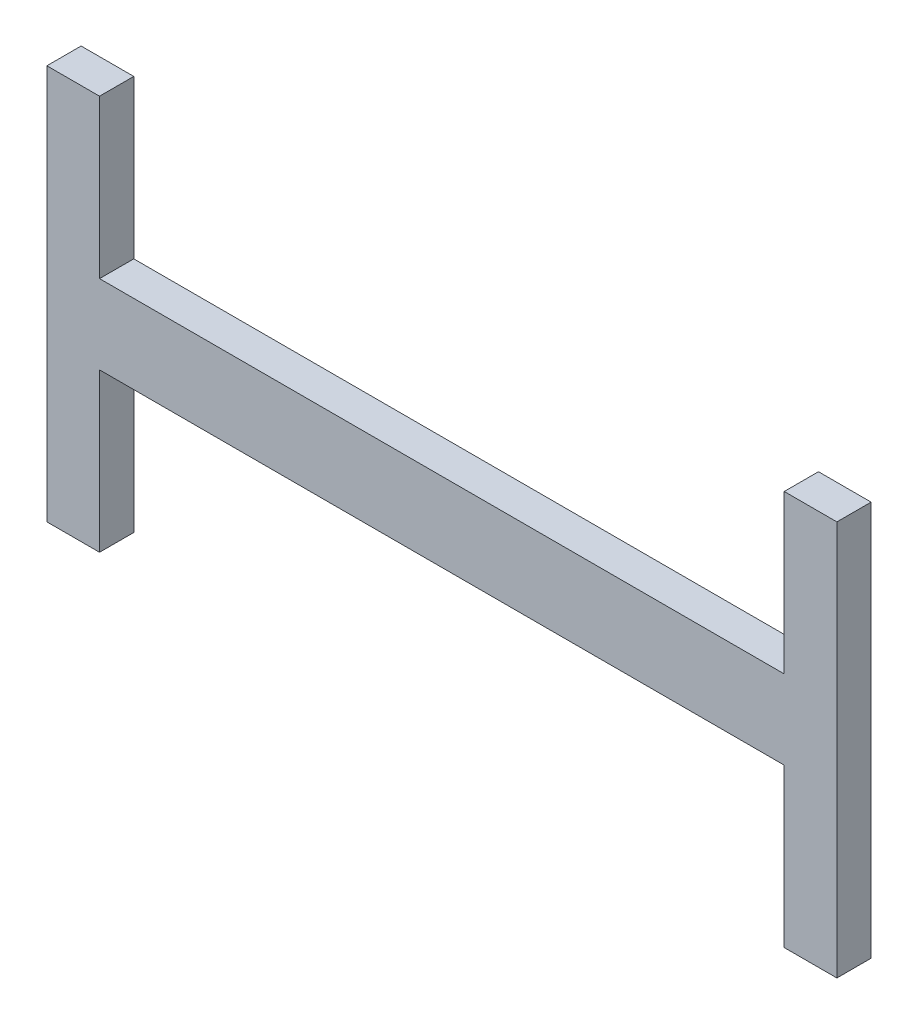
SolidWorks part; units mm, degrees
ref_plane "Plan de face" through (0, 0, 0) normal (0, 0, 1) x (1, 0, 0)
ref_plane "Plan de dessus" through (0, 0, 0) normal (0, 1, 0) x (1, 0, 0)
ref_plane "Plan de droite" through (0, 0, 0) normal (1, 0, 0) x (0, 0, -1)
sketch "Esquisse1" plane through (0, 0, 0) normal (0, 0, 1) x (1, 0, 0)
  line L1 (0, 0) -> (3000, 0)
  line L2 (0, 0) -> (0, 1500)
  line L3 (0, 1500) -> (3000, 1500)
  line L4 (3000, 0) -> (3000, 1500)
  dimension "D1" = 3000
  dimension "D2" = 1500
extrude "Boss.-Extru.1" add sketch "Esquisse1" against normal blind 130 contours L3 L4 L1 L2
sketch "Esquisse3" plane through (0, 0, 0) normal (0, 0, 1) x (1, 0, 0)
  line L0 (200, 1500) -> (200, 900)
  line L1 (0, 1500) -> (3000, 1500) construction
  line L2 (200, 900) -> (2800, 900)
  line L3 (2800, 900) -> (2800, 1500)
  line L4 (200, 1500) -> (2800, 1500)
  line L5 (0, 0) -> (0, 1500) construction
  line L6 (3000, 0) -> (3000, 1500) construction
  line L7 (200, 0) -> (200, 600)
  line L8 (0, 0) -> (3000, 0) construction
  line L9 (200, 600) -> (2800, 600)
  line L10 (2800, 600) -> (2800, 0)
  line L11 (200, 0) -> (2800, 0)
  dimension "D1" = 200
  dimension "D2" = 200
  dimension "D3" = 300
  dimension "D4" = 600
extrude "Enlèv. mat.-Extru.1" cut sketch "Esquisse3" against normal blind 130 contours L7 L11 L10 L9 | L2 L3 L4 L0 region at (1500, 300, 0)
